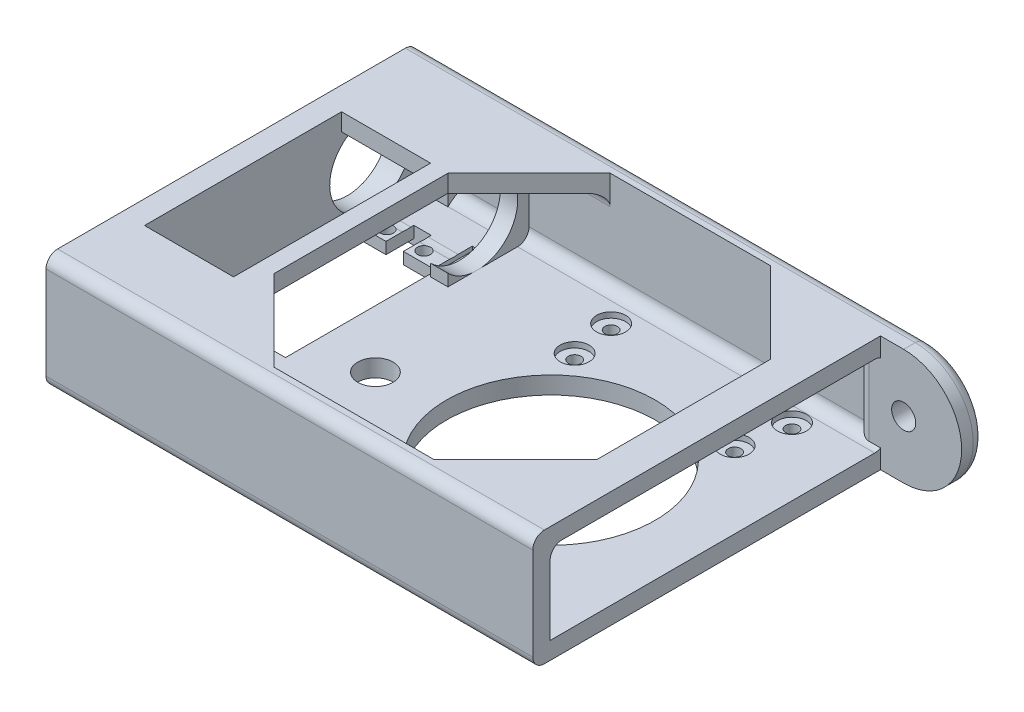
SolidWorks part; units mm, degrees
ref_plane "Front Plane" through (0, 0, 0) normal (0, 0, 1) x (1, 0, 0)
ref_plane "Top Plane" through (0, 0, 0) normal (0, 1, 0) x (1, 0, 0)
ref_plane "Right Plane" through (0, 0, 0) normal (1, 0, 0) x (0, 0, -1)
sketch "Sketch1" plane through (0, 0, 0) normal (0, 1, 0) x (1, 0, 0)
  line L0 (66.675, 50.8) -> (-66.675, -50.8) construction
  line L1 (-66.675, 50.8) -> (66.675, 50.8)
  line L2 (-66.675, 50.8) -> (-66.675, -50.8)
  line L3 (-66.675, -50.8) -> (66.675, -50.8)
  line L4 (66.675, 50.8) -> (66.675, -50.8)
  dimension "D1" = 133.35
  dimension "D2" = 101.6
extrude "Top" add sketch "Sketch1" along normal blind 4.7625
sketch "Sketch2" plane through (0, 0, 0) normal (0, 1, 0) x (1, 0, 0)
  line L0 (66.675, 50.8) -> (66.675, 46.0375)
  line L1 (-66.675, 50.8) -> (66.675, 50.8)
  line L2 (-66.675, 50.8) -> (-66.675, -50.8)
  line L3 (-66.675, -50.8) -> (66.675, -50.8)
  line L4 (66.675, -50.8) -> (66.675, 50.8) construction
  line L5 (66.675, -50.8) -> (66.675, -46.0375)
  line L7 (66.675, -46.0375) -> (-60.325, -46.0375) construction
  line L8 (-60.325, -46.0375) -> (-60.325, 46.0375)
  line L9 (66.675, 46.0375) -> (-60.325, 46.0375) construction
  line L10 (-35.941, 46.0375) -> (-35.941, 23.8125)
  line L11 (-35.941, 23.8125) -> (-31.1785, 23.8125)
  line L12 (-31.1785, 23.8125) -> (-31.1785, 46.0375)
  line L13 (66.675, 46.0375) -> (-31.1785, 46.0375)
  line L14 (-35.941, 46.0375) -> (-60.325, 46.0375)
  line L15 (-47.117, -46.0375) -> (-47.117, -30.1625)
  line L16 (-47.117, -30.1625) -> (-42.3545, -30.1625)
  line L17 (-42.3545, -30.1625) -> (-42.3545, -46.0375)
  line L18 (-60.325, -46.0375) -> (-47.117, -46.0375)
  line L19 (-42.3545, -46.0375) -> (66.675, -46.0375)
  dimension "D1" = 4.7625
  dimension "D2" = 4.7625
  dimension "D3" = 24.384
  dimension "D4" = 22.225
  dimension "D5" = 15.875
  dimension "D6" = 13.208
  dimension "D7" = 6.35
extrude "Walls" add sketch "Sketch2" along normal blind 31.75
sketch "Sketch4" plane through (0, 31.75, 0) normal (0, 1, 0) x (1, 0, 0)
  line L0 (66.675, 50.8) -> (66.675, -50.8)
  line L1 (66.675, -50.8) -> (57.15, -50.8)
  line L2 (-66.675, -50.8) -> (66.675, -50.8) construction
  line L3 (57.15, -50.8) -> (57.15, 50.8) construction
  line L4 (66.675, 50.8) -> (-66.675, 50.8) construction
  line L6 (57.15, 50.8) -> (66.675, 50.8)
  line L7 (-35.941, -46.0375) -> (-35.941, 46.0375) construction
  line L9 (-35.941, 46.0375) -> (-31.1785, 46.0375)
  line L10 (-31.1785, 46.0375) -> (-31.1785, -46.0375) construction
  line L11 (66.675, -46.0375) -> (-42.3545, -46.0375) construction
  line L12 (-31.1785, -46.0375) -> (-35.941, -46.0375)
  line L13 (-35.941, -30.1625) -> (-60.325, -30.1625)
  line L14 (-60.325, -46.0375) -> (-60.325, 46.0375) construction
  line L15 (-42.3545, -30.1625) -> (-47.117, -30.1625) construction
  line L16 (-35.941, -46.0375) -> (-60.325, -46.0375)
  line L17 (-60.325, -46.0375) -> (-60.325, -30.1625)
  line L18 (-35.941, 23.8125) -> (-60.325, 23.8125)
  line L19 (-60.325, 23.8125) -> (-60.325, 46.0375)
  line L20 (-60.325, 46.0375) -> (-35.941, 46.0375)
  line L21 (-35.941, 23.8125) -> (-35.941, -30.1625)
  line L22 (-31.1785, 23.8125) -> (-8.9535, 46.0375)
  line L23 (-31.1785, 46.0375) -> (66.675, 46.0375) construction
  line L24 (-8.9535, 46.0375) -> (-31.1785, 46.0375)
  line L26 (-31.1785, -23.8125) -> (-8.9535, -46.0375)
  line L27 (-8.9535, -46.0375) -> (-31.1785, -46.0375)
  line L28 (-31.1785, 23.8125) -> (-31.1785, -23.8125)
  line L29 (-31.1785, -23.8125) -> (57.15, -23.8125) construction
  line L30 (-31.1785, 23.8125) -> (57.15, 23.8125) construction
  line L31 (57.15, 23.8125) -> (30.1625, 50.8)
  line L32 (30.1625, 50.8) -> (57.15, 50.8)
  line L33 (57.15, -23.8125) -> (30.1625, -50.8)
  line L34 (30.1625, -50.8) -> (57.15, -50.8)
  line L35 (57.15, 23.8125) -> (57.15, -23.8125)
  dimension "D1" = 9.525
  dimension "D2" = 45
  dimension "D3" = 45
  dimension "D4" = 22.225
  dimension "D5" = 45
  dimension "D6" = 45
extrude "Bottom" add sketch "Sketch4" against normal blind 4.7625
sketch "Sketch9" plane through (0, 0, -50.8) normal (0, 0, -1) x (-1, 0, 0)
  line L0 (-66.675, 15.875) -> (-73.025, 15.875) construction
  line L2 (-73.025, 31.75) -> (-63.5, 31.75)
  line L3 (-73.025, 0) -> (-63.5, 0)
  line L4 (-66.675, 31.75) -> (-66.675, 0) construction
  line L5 (-66.675, 0) -> (66.675, 0) construction
  line L6 (-66.675, 31.75) -> (66.675, 31.75) construction
  line L8 (-63.5, 31.75) -> (-63.5, 0)
  circle A0 centre (-73.025, 15.875) radius 15.875 construction
  arc A1 (-73.025, 31.75) -> (-73.025, 0) centre (-73.025, 15.875) ccw
  circle A2 centre (-73.025, 15.875) radius 3.302
  dimension "D3" = 6.604
  dimension "D1" = 6.35
extrude "Joint Hinge" add sketch "Sketch9" against normal blind 6.35
sketch "Screw Locs" plane through (0, 31.75, 0) normal (0, 1, 0) x (1, 0, 0)
  line L0 (73.025, 50.8) -> (-66.675, 50.8) construction
  line L1 (-66.675, -50.8) -> (66.675, -50.8) construction
  line L2 (66.675, -50.8) -> (66.675, 44.45) construction
  line L3 (73.025, 50.8) -> (-66.675, 50.8) construction
  line L4 (-66.675, 50.8) -> (-66.675, -50.8) construction
  point P0 (-63.5, 12.7)
  point P1 (-63.5, -25.4)
  point P6 (-63.5, 47.625)
  point P7 (-63.5, -47.625)
  point P10 (63.5, 47.625)
  point P11 (63.5, -47.625)
  dimension "D2" = 25.4
  dimension "D1" = 38.1
  dimension "D3" = 3.175
  dimension "D4" = 3.175
  dimension "D5" = 3.175
  dimension "D6" = 3.175
  dimension "D7" = 3.175
  dimension "D8" = 3.175
sketch "Sketch3" plane through (-66.675, 0, 0) normal (-1, 0, 0) x (0, 0, 1)
  line L0 (-50.8, 15.875) -> (-31.75, 15.875) construction
  line L1 (-50.8, 31.75) -> (-50.8, 0) construction
  line L2 (50.8, 15.875) -> (38.1, 15.875) construction
  line L3 (50.8, 31.75) -> (50.8, 0) construction
  line L4 (-31.75, 15.875) -> (-31.75, 0) construction
  line L7 (-50.8, 0) -> (50.8, 0) construction
  circle A0 centre (38.1, 15.875) radius 6.604
  circle A1 centre (-31.75, 15.875) radius 11.176
  dimension "D3" = 13.208
  dimension "D4" = 22.352
  dimension "D1" = 19.05
  dimension "D2" = 12.7
  dimension "D5" = 15.875
extrude "Shaft holes" cut sketch "Sketch3" against normal up to vertex (35.4965 mm away) up to point (-31.1785, 4.7625, -23.8125)
sketch "Sketch21" plane through (0, 4.7625, 0) normal (0, 1, 0) x (1, 0, 0)
  line L1 (-60.325, 26.67) -> (-58.7375, 26.67)
  line L2 (-60.325, 26.67) -> (-60.325, 36.83)
  line L3 (-60.325, 36.83) -> (-58.7375, 36.83)
  line L4 (-58.7375, 26.67) -> (-58.7375, 36.83)
  line L5 (-37.5285, 26.67) -> (-35.941, 26.67)
  line L6 (-37.5285, 26.67) -> (-37.5285, 36.83)
  line L7 (-37.5285, 36.83) -> (-35.941, 36.83)
  line L8 (-35.941, 26.67) -> (-35.941, 36.83)
  line L9 (-60.325, 31.75) -> (-66.675, 31.75) construction
  line L10 (-60.325, 30.5603) -> (-60.325, -46.0375) construction
  line L11 (-35.941, 23.8125) -> (-35.941, 30.5603) construction
  point P10 (-60.325, 31.75)
  dimension "D1" = 1.5875
  dimension "D2" = 10.16
extrude "Retaining Ring Cut" cut sketch "Sketch21" against normal blind 1.1906 and the other way blind 23.4156
sketch "Sketch10" plane through (0, 0, 0) normal (0, 1, 0) x (1, 0, 0)
  line L2 (-60.325, 31.75) -> (-66.675, 31.75) construction
  line L3 (-60.325, -46.0375) -> (-60.325, 26.67) construction
  line L4 (-48.1012, 15.748) -> (-20.8924, -6.35) construction
  circle A0 centre (-20.8924, -6.35) radius 4.826
  line B0 (-59.5312, 26.138) -> (-59.5312, -15.202)
  line B1 (-36.6712, 26.138) -> (-36.6712, -15.202)
  circle B2 centre (-43.0162, 29.09) radius 1.778
  circle B3 centre (-53.1862, 29.09) radius 1.778
  circle B4 centre (-43.0162, -18.154) radius 1.778
  circle B5 centre (-53.1862, -18.154) radius 1.778
  line B6 (-59.5312, 26.138) -> (-50.4825, 26.138)
  line B7 (-36.6712, 26.138) -> (-45.72, 26.138)
  line B8 (-50.4825, 26.138) -> (-50.4825, 33.758)
  line B9 (-50.4825, 33.758) -> (-45.72, 33.758)
  line B10 (-45.72, 33.758) -> (-45.72, 26.138)
  line B11 (-45.72, -15.202) -> (-45.72, -22.822)
  line B12 (-45.72, -22.822) -> (-50.4825, -22.822)
  line B13 (-50.4825, -22.822) -> (-50.4825, -15.202)
  line B14 (-36.6712, -15.202) -> (-45.72, -15.202)
  line B15 (-50.4825, -15.202) -> (-59.5312, -15.202)
  dimension "D1" = 16.002
  dimension "D5" = 9.652
  dimension "D2" = 0.7937
  dimension "D3" = 35.052
  dimension "D4" = 38.1
sketch_block_instance "Servo Mount ABS underside-3"
sketch_block "Servo Mount ABS underside" parameters "D5"=3.556, "D7"=1.8773, "D1"=22.86, "D2"=41.34, "D3"=10.17, "D4"=47.244, "D6"=10.39, "D8"=7.7865, "D9"=5.4364
extrude "Actuator Mount" cut sketch "Sketch10" along normal blind 12.7
sketch "Sketch14" plane through (0, 31.75, 0) normal (0, 1, 0) x (1, 0, 0)
  circle A0 centre (63.5, 47.625) radius 3.175
  circle A1 centre (63.5, -47.625) radius 3.175
  dimension "D1" = 6.35
extrude "Screw Pillar" add sketch "Sketch14" against normal through all
sketch "Sketch15" plane through (0, 0, 0) normal (0, 1, 0) x (1, 0, 0)
  line L1 (-36.6712, 33.758) -> (-59.5312, 33.758)
  line L2 (-36.6712, 33.758) -> (-36.6712, -22.822)
  line L3 (-36.6712, -22.822) -> (-59.5312, -22.822)
  line L4 (-59.5312, 33.758) -> (-59.5312, -22.822)
  line L6 (-36.6712, -15.202) -> (-36.6712, 26.138) construction
  line L9 (-59.5312, 26.138) -> (-59.5312, -15.202) construction
  line L10 (-50.4825, -22.822) -> (-45.72, -22.822) construction
  line L11 (-45.72, 33.758) -> (-50.4825, 33.758) construction
extrude "Servo Inset" cut sketch "Sketch15" along normal blind 1.5875
sketch "Sketch11" plane through (0, 0, 0) normal (0, -1, 0) x (1, 0, 0)
  line L0 (66.675, 50.8) -> (66.675, -44.45) construction
  line L1 (24.003, 3.175) -> (66.675, 3.175) construction
  line B0 (-1.232, -28.57) -> (49.238, -28.57) construction
  line B1 (49.238, -28.57) -> (49.238, 34.92) construction
  line B2 (49.238, 34.92) -> (-1.232, 34.92) construction
  line B3 (-1.232, 34.92) -> (-1.232, -28.57) construction
  line B4 (-1.232, 34.92) -> (49.238, -28.57) construction
  circle B5 centre (1.943, -25.395) radius 1.5875 construction
  circle B6 centre (45.758, -25.395) radius 1.5875 construction
  circle B7 centre (1.943, 31.755) radius 1.5875 construction
  circle B8 centre (45.758, 31.755) radius 1.5875 construction
  circle B9 centre (48.133, 43.815) radius 1.6 construction
  circle B10 centre (-0.127, -37.465) radius 1.6 construction
  circle B11 centre (-0.127, 37.465) radius 1.6 construction
  circle B12 centre (48.133, -38.735) radius 1.6 construction
  arc B13 (49.673, -52.832) -> (50.8, -51.705) centre (49.673, -51.705) ccw construction
  line B14 (-0.127, -37.465) -> (48.133, 43.815) construction
sketch_block_instance "Block-PDM-1"
sketch_block "Block-PDM"
sketch_block_instance "Block-Hole Pattern-1"
sketch_block "Block-Hole Pattern"
sketch_block_instance "Holes-2-2"
sketch_block "Holes-2"
sketch "Sketch13" plane through (0, 0, 0) normal (0, -1, 0) x (1, 0, 0)
  line L1 (-57.15, 26.67) -> (-55.372, 26.67)
  line L2 (-57.15, 26.67) -> (-57.15, 31.75)
  line L3 (-57.15, 31.75) -> (-55.372, 31.75)
  line L4 (-55.372, 26.67) -> (-55.372, 31.75)
  line L5 (-66.675, 50.8) -> (66.675, 50.8) construction
  line L6 (-66.675, -50.8) -> (-66.675, 50.8) construction
  dimension "D1" = 1.778
  dimension "D2" = 5.08
  dimension "D3" = 19.05
  dimension "D4" = 9.525
extrude "Wire Loft Mount" cut sketch "Sketch13" against normal blind 12.7
hole_wizard "CBORE for #4 Hex Machine Screw1" positions "Sketch19" profile "Sketch20" counterbore size "#4" standard "ANSI Inch" end condition through all
sketch "Sketch19" plane through (19.8448, 4.7625, 10.3049) normal (0, -1, 0) x (-1, 0, 0)
  point P0 (-28.2882, -33.5101)
  point P3 (-25.9132, -21.4501)
  point P6 (19.9718, -27.1601)
  point P9 (17.9018, -21.4501)
  point P12 (17.9018, 35.6999)
  point P15 (19.9718, 47.7699)
  point P18 (-25.9132, 35.6999)
  point P21 (-28.2882, 49.0399)
sketch "Sketch20" plane through (48.133, 4.7625, 43.815) normal (1, 0, 0) x (0, 0, 1)
  line L0 (0, 0) -> (0, 4.7625)
  line L1 (1.7272, 4.1275) -> (2.3622, 4.7625)
  line L2 (1.7272, 4.1275) -> (1.7272, 1.524)
  line L3 (1.7272, 1.524) -> (3.9688, 1.524)
  line L4 (3.9688, 1.524) -> (3.9688, 0)
  line L5 (3.9688, 0) -> (0, 0)
  line L11 (0, -6.35) -> (0, 107.95) construction
  line L12 (2.3622, 4.7625) -> (0, 4.7625)
  line L13 (-1.7272, 4.1275) -> (-2.3622, 4.7625) construction
  dimension "Thru Hole Dia." = 3.4544
  dimension "Thru Hole Depth" = 4.7625
  dimension "C'Bore Dia." = 7.9375
  dimension "C'Bore Depth" = 1.524
  dimension "Far C'Sink Dia." = 4.7244
  dimension "Far C'Sink Angle" = 90
fillet "Fillet1" radius 3.175 14 edges at (0, 0, 50.8) (3.175, 0, -50.8) (14.7859, 4.7625, -46.0375) (-53.721, 4.7625, 46.0375) (-48.133, 4.7625, -46.0375) (-48.133, 26.9875, -46.0375) (-20.066, 26.9875, -46.0375) (47.8377, 26.9875, -46.0375) (-25.654, 26.9875, 46.0375) (47.8377, 26.9875, 46.0375) (1.2452, 4.7625, 46.0375) (3.175, 31.75, -50.8) (0, 31.75, 50.8) (88.9, 15.875, -50.8)
sketch "Sketch22" plane through (0, 0, 0) normal (0, -1, 0) x (1, 0, 0)
  circle A0 centre (24.003, 3.175) radius 28.575
  dimension "D1" = 57.15
extrude "Strain Relief" cut sketch "Sketch22" against normal up to next
